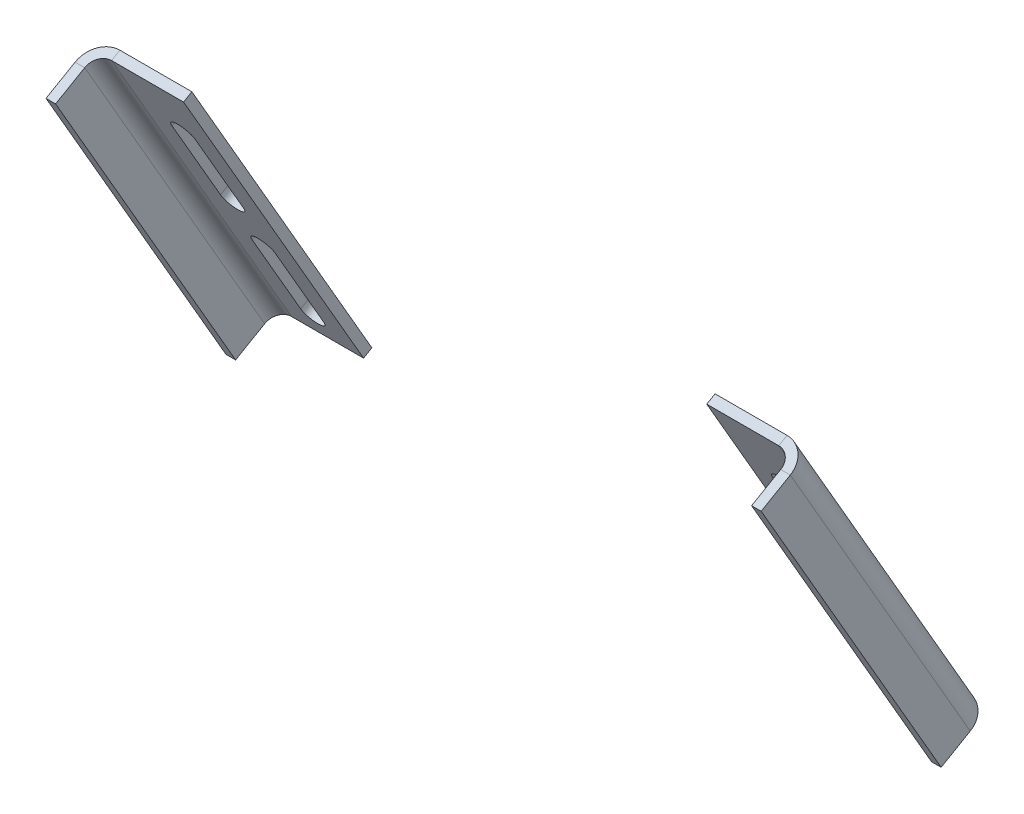
SolidWorks part; units mm, degrees
note: The reader was unsure of these and kept them because the rebuilt part matched: flange length of "邊線-凸緣2", "邊線-凸緣3".
material "AISI 4130 Steel, normalized at 870C"
ref_plane "Front Plane" through (0, 0, 0) normal (0, 0, 1) x (1, 0, 0)
ref_plane "Top Plane" through (0, 0, 0) normal (0, 1, 0) x (1, 0, 0)
ref_plane "Right Plane" through (0, 0, 0) normal (1, 0, 0) x (0, 0, -1)
sketch3d "3DSketch1"
  line L6 (62, 664.3499, -730) -> (62, 664.3499, -742.7) construction
  line L7 (-62, 664.3499, -730) -> (-62, 664.3499, -742.7) construction
  line L10 (168.1941, 654.6322, -730) -> (7.1882, 669.3432, -730) construction
  line L11 (-7.1882, 669.3432, -730) -> (-168.1941, 654.6322, -730) construction
  line L12 (-62, 664.3499, -742.7) -> (-62, 601.13, -779.2)
  line L13 (62, 664.3499, -742.7) -> (61.9933, 601.13, -779.2)
  line L14 (-62, 601.13, -779.2) -> (61.9933, 601.13, -779.2) construction
  point P3 (0, 0, 0)
  point P4 (0, 0, 0)
  point P6 (0, 0, 0)
  point P7 (0, 0, 0)
  dimension "D1" = 120
  dimension "D2" = 120
  dimension "D3" = 73
ref_plane "Plane1" through (0, 487.686, -844.6969) normal (0, 0.5, -0.866) x (-1, 0, 0)
sketch "Sketch2" plane through (0, 487.686, -844.6969) normal (0, 0.5, -0.866) x (-1, 0, 0)
  line L2 (-54.5, 203.9939) -> (-54.5, 128.9939)
  line L3 (-54.5, 128.9939) -> (-69.5, 128.9939)
  line L4 (-69.5, 203.9939) -> (-69.5, 128.9939)
  line L5 (-61.9966, 174.8292) -> (-61.9966, 188.9939) construction
  line L6 (-61.9966, 174.8292) -> (-61.9966, 163.9939) construction
  line L7 (-59.5966, 186.5939) -> (-59.5966, 166.3939)
  line L8 (-64.3966, 186.5939) -> (-64.3966, 166.3939)
  line L9 (-59.5966, 186.5939) -> (-64.3966, 186.5939) construction
  line L10 (-59.5966, 166.3939) -> (-64.3966, 166.3939) construction
  line L11 (-62, 203.9939) -> (-61.9933, 130.9939) construction
  line L13 (-59.5956, 135.3939) -> (-64.3956, 135.3939) construction
  line L14 (-59.5956, 155.5939) -> (-64.3956, 155.5939) construction
  line L15 (-59.5956, 155.5939) -> (-59.5956, 135.3939)
  line L16 (-64.3956, 135.3939) -> (-64.3956, 155.5939)
  line L17 (-54.5, 203.9939) -> (-69.5, 203.9939)
  arc A8 (-59.5966, 186.5939) -> (-64.3966, 186.5939) centre (-61.9966, 186.5939) ccw
  arc A9 (-59.5966, 166.3939) -> (-64.3966, 166.3939) centre (-61.9966, 166.3939) cw
  arc A10 (-59.5956, 135.3939) -> (-64.3956, 135.3939) centre (-61.9956, 135.3939) cw
  arc A11 (-59.5956, 155.5939) -> (-64.3956, 155.5939) centre (-61.9956, 155.5939) ccw
  point P4 (0, 0)
  point P5 (0, 0)
  point P9 (-61.9966, 188.9939)
  point P13 (-61.9966, 163.9939)
  point P14 (0, 0)
  point P15 (0, 0)
  point P16 (0, 0)
  point P17 (0, 0)
  point P18 (0, 0)
  point P19 (0, 0)
  point P33 (-61.9956, 132.9939)
  point P37 (-61.9956, 157.9939)
  dimension "D4" = 2.4
  dimension "D7" = 2.4
  dimension "D11" = 2.4
  dimension "D12" = 2.4
  dimension "D3" = 15
  dimension "D5" = 4
  dimension "D1" = 15
  dimension "D2" = 75
  dimension "D6" = 25
  dimension "D8" = 4.8
  dimension "D9" = 25
  dimension "D13" = 4.8
sketch "Sketch12" plane through (0, 487.686, -844.6969) normal (0, 0.5, -0.866) x (-1, 0, 0)
  line L0 (62, 203.9939) -> (62, 130.9939) construction
  line L25 (59.6, 155.5939) -> (64.4, 155.5939) construction
  line L26 (59.6, 135.3939) -> (64.4, 135.3939) construction
  line L27 (59.6, 188.9939) -> (64.4, 188.9939) construction
  line L28 (59.6, 168.7939) -> (64.4, 168.7939) construction
  line L29 (54.5, 203.9939) -> (69.5, 203.9939)
  line L30 (69.5, 203.9939) -> (69.5, 128.9939)
  line L31 (54.5, 203.9939) -> (54.5, 128.9939)
  line L32 (54.5, 128.9939) -> (69.5, 128.9939)
  line L33 (59.6, 155.5939) -> (59.6, 135.3939)
  line L34 (64.4, 135.3939) -> (64.4, 155.5939)
  line L35 (59.6, 188.9939) -> (59.6, 168.7939)
  line L36 (64.4, 188.9939) -> (64.4, 168.7939)
  arc A8 (59.6, 155.5939) -> (64.4, 155.5939) centre (62, 155.5939) cw
  arc A9 (64.4, 135.3939) -> (59.6, 135.3939) centre (62, 135.3939) cw
  arc A10 (64.4, 168.7939) -> (59.6, 168.7939) centre (62, 168.7939) cw
  arc A11 (59.6, 188.9939) -> (64.4, 188.9939) centre (62, 188.9939) cw
  point P0 (0, 0)
  point P42 (62, 191.3939)
  point P43 (62, 166.3939)
  point P44 (62, 157.9939)
  point P45 (62, 132.9939)
  dimension "D3" = 2.4
  dimension "D4" = 2.4
  dimension "D7" = 2.4
  dimension "D8" = 2.4
  dimension "D9" = 7.5
  dimension "D10" = 4
  dimension "D1" = 15
  dimension "D2" = 75
  dimension "D5" = 4.8
  dimension "D6" = 4.8
  dimension "D11" = 25
  dimension "D12" = 25
  dimension "D13" = 15
  dimension "D14" = 7.5
base flange "Base-Flange2" sketch "Sketch2" thickness 2 reverse thickness direction no parameters "D1"=0.7366
edge flange "邊線-凸緣2" sketch "Sketch17" flange angle 90 flange length 12 flange position bend outside bend radius 3 thickness 2 relief rectangular parameters "D6"=10
sketch "Sketch17" plane through (69.5, 486.686, -842.9649) normal (1, 0, 0) x (0, 0.866, 0.5)
  line L0 (203.9939, 0) -> (128.9939, 0) construction
  line L1 (203.9939, 0) -> (128.9939, 0)
  line L2 (128.9939, 0) -> (128.9939, 10)
  line L3 (128.9939, 10) -> (203.9939, 10)
  line L4 (203.9939, 10) -> (203.9939, 0)
bend "邊線彎折2" bend radius 3 bend angle 90 parameters "D5"=1
base flange "Base-Flange3" sketch "Sketch12" thickness 2 reverse thickness direction no parameters "D1"=0.7366
edge flange "邊線-凸緣3" sketch "Sketch22" flange angle 90 flange length 12 flange position bend outside bend radius 3 thickness 2 relief rectangular parameters "D6"=10
sketch "Sketch22" plane through (-69.5, 486.686, -842.9649) normal (-1, 0, 0) x (0, -0.866, -0.5)
  line L0 (-128.9939, 0) -> (-203.9939, 0) construction
  line L1 (-128.9939, 0) -> (-203.9939, 0)
  line L2 (-203.9939, 0) -> (-203.9939, 10)
  line L3 (-203.9939, 10) -> (-128.9939, 10)
  line L4 (-128.9939, 10) -> (-128.9939, 0)
bend "邊線彎折3" bend radius 3 bend angle 90 parameters "D5"=1
sketch "彎折-線1" [suppressed] plane through (0, 0, 0) normal (0, 1, 0) x (1, 0, 0)
sketch "邊界方塊1" [suppressed] plane through (0, 0, 0) normal (0, 1, 0) x (1, 0, 0)
sheet metal parameters "鈑金3" thickness 2 parameters "D1"=0.7366
flat pattern "平板-型式3" [suppressed]
sketch "彎折-線3" plane through (0, 0, 0) normal (0, 1, 0) x (1, 0, 0)
sketch3d "邊界方塊3" [suppressed]
  line L0 (53.9129, 200.2268, 0) -> (53.9129, 125.2268, 0) construction
  line L1 (68.9129, 200.2268, 0) -> (68.9129, 125.2268, 0) construction
  line L2 (53.9129, 200.2268, 0) -> (68.9129, 200.2268, 0) construction
  line L3 (53.9129, 125.2268, 0) -> (68.9129, 125.2268, 0) construction
sheet metal parameters "鈑金4" thickness 2 parameters "D1"=0.7366
flat pattern "平板-型式3"
sketch "彎折-線3" plane through (0, 487.686, -844.6969) normal (0, 0.5, -0.866) x (-1, 0, 0)
  line L0 (-71, 203.9939) -> (-71, 128.9939) construction
  line L1 (-71, 203.9939) -> (-71, 128.9939) construction
sketch3d "邊界方塊3" [suppressed]
  line L0 (-54.5, 203.9939, 0) -> (-54.5, 128.9939, 0) construction
  line L1 (-79.5, 203.9939, 0) -> (-79.5, 128.9939, 0) construction
  line L2 (-54.5, 203.9939, 0) -> (-79.5, 203.9939, 0) construction
  line L3 (-54.5, 128.9939, 0) -> (-79.5, 128.9939, 0) construction
bend of the flat pattern "平板-<邊線彎折2>1"
sheet metal parameters "鈑金5" thickness 2 parameters "D1"=0.7366
flat pattern "平板-型式5"
sketch "彎折-線4" plane through (0, 0, 0) normal (0, 1, 0) x (1, 0, 0)
sketch3d "邊界方塊4" [suppressed]
  line L0 (-68.9129, 200.2268, 0) -> (-68.9129, 125.2268, 0) construction
  line L1 (-53.9129, 200.2268, 0) -> (-53.9129, 125.2268, 0) construction
  line L2 (-68.9129, 200.2268, 0) -> (-53.9129, 200.2268, 0) construction
  line L3 (-68.9129, 125.2268, 0) -> (-53.9129, 125.2268, 0) construction
sheet metal parameters "鈑金6" thickness 2 parameters "D1"=0.7366
flat pattern "平板-型式5"
sketch "彎折-線4" plane through (0, 487.686, -844.6969) normal (0, 0.5, -0.866) x (-1, 0, 0)
  line L0 (71, 128.9939) -> (71, 203.9939) construction
  line L1 (71, 128.9939) -> (71, 203.9939) construction
sketch3d "邊界方塊4" [suppressed]
  line L0 (79.5, 203.9939, 0) -> (79.5, 128.9939, 0) construction
  line L1 (54.5, 203.9939, 0) -> (54.5, 128.9939, 0) construction
  line L2 (79.5, 203.9939, 0) -> (54.5, 203.9939, 0) construction
  line L3 (79.5, 128.9939, 0) -> (54.5, 128.9939, 0) construction
bend of the flat pattern "平板-<邊線彎折3>1"
